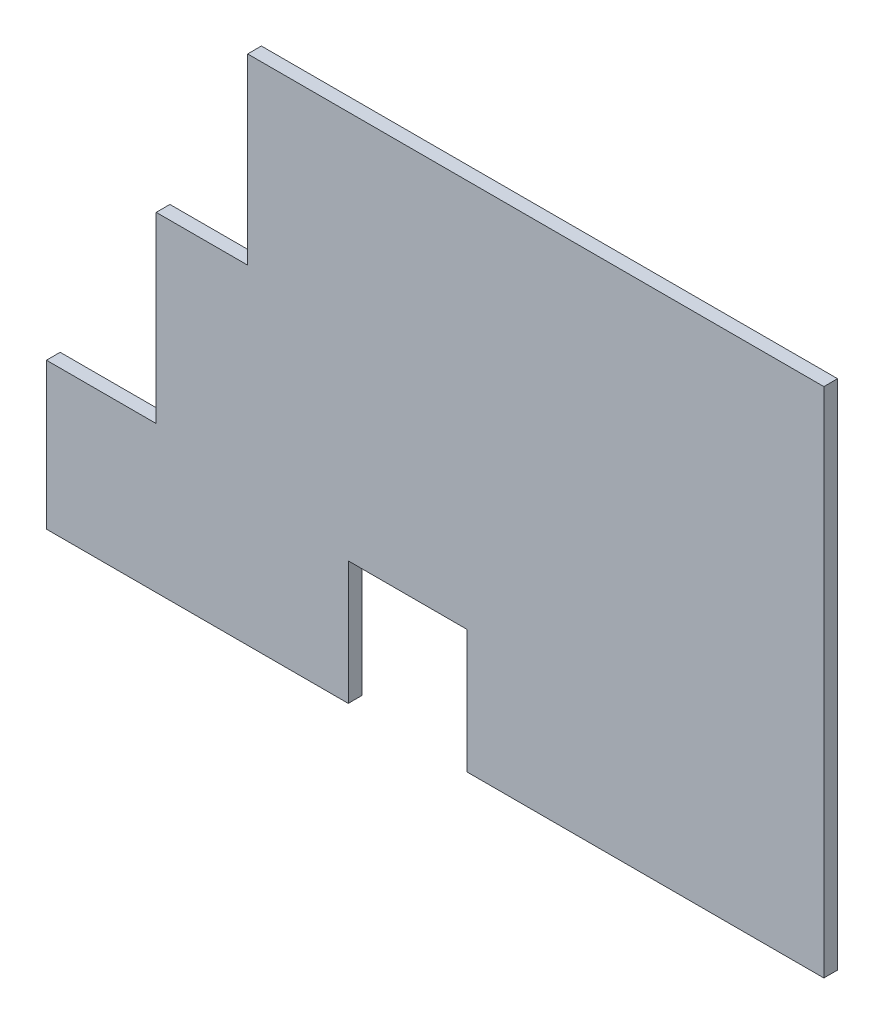
SolidWorks part; units mm, degrees
ref_plane "Płaszczyzna przednia" through (0, 0, 0) normal (0, 0, 1) x (1, 0, 0)
ref_plane "Płaszczyzna górna" through (0, 0, 0) normal (0, 1, 0) x (1, 0, 0)
ref_plane "Płaszczyzna prawa" through (0, 0, 0) normal (1, 0, 0) x (0, 0, -1)
sketch "Szkic1" plane through (0, 0, 0) normal (0, 0, 1) x (1, 0, 0)
  line L0 (9.0136, -46.0996) -> (48.0136, -46.0996)
  line L1 (48.0136, -46.0996) -> (48.0136, 9.9004)
  line L2 (48.0136, 9.9004) -> (-14.9864, 9.9004)
  line L3 (-14.9864, 9.9004) -> (-14.9864, -10.0996)
  line L4 (-14.9864, -10.0996) -> (-24.9864, -10.0996)
  line L5 (-24.9864, -10.0996) -> (-24.9864, -30.0996)
  line L6 (-24.9864, -30.0996) -> (-36.9864, -30.0996)
  line L7 (-36.9864, -30.0996) -> (-36.9864, -46.0996)
  line L8 (-36.9864, -46.0996) -> (-3.9864, -46.0996)
  line L9 (-3.9864, -46.0996) -> (-3.9864, -32.5996)
  line L10 (-3.9864, -32.5996) -> (9.0136, -32.5996)
  line L11 (9.0136, -46.0996) -> (9.0136, -32.5996)
  dimension "D3" = 13
  dimension "D4" = 13.5
  dimension "D5" = 33
  dimension "D6" = 63
  dimension "D7" = 10
  dimension "D1" = 56
  dimension "D2" = 39
  dimension "D8" = 16
  dimension "D9" = 20
extrude "Dodanie-wyciągnięcie1" add sketch "Szkic1" along normal blind 1.5
